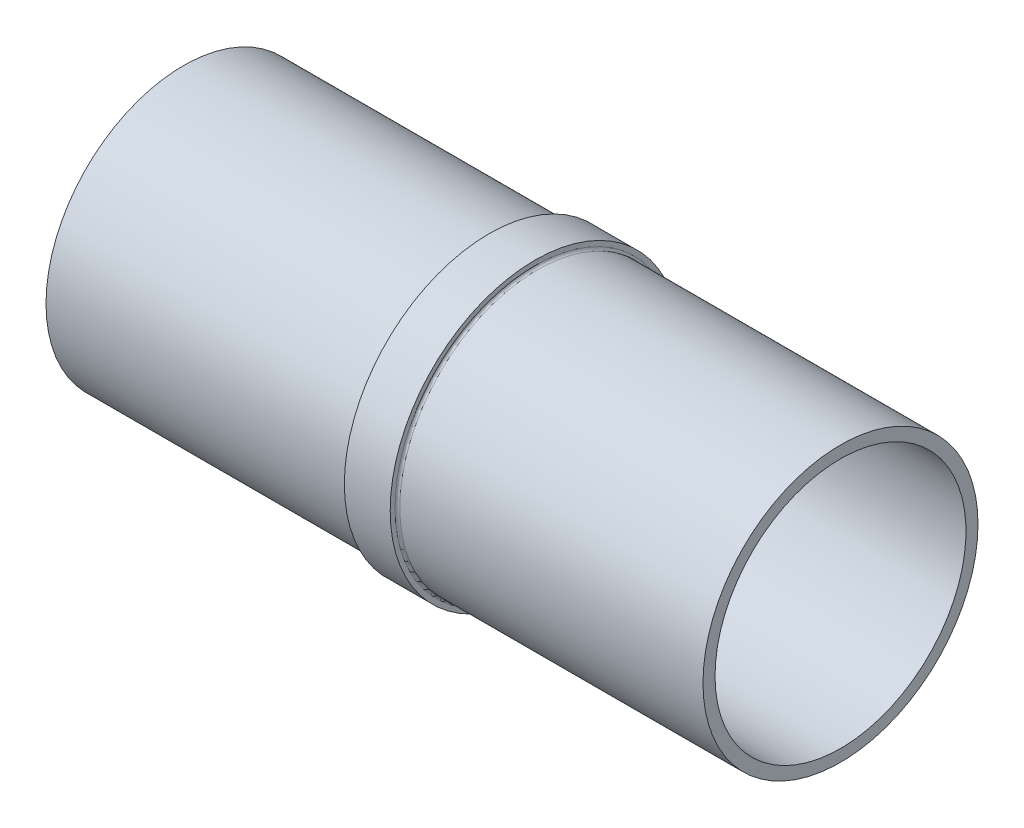
SolidWorks part; units mm, degrees
ref_plane "Front Plane" through (0, 0, 0) normal (0, 0, 1) x (1, 0, 0)
ref_plane "Top Plane" through (0, 0, 0) normal (0, 1, 0) x (1, 0, 0)
ref_plane "Right Plane" through (0, 0, 0) normal (1, 0, 0) x (0, 0, -1)
sketch "Sketch1" plane through (0, 0, 0) normal (0, 1, 0) x (1, 0, 0)
  line L1 (0, -34.1825) -> (0, 34.1825) construction
  line L2 (0, 52.15) -> (-74.2, 52.15)
  line L3 (-76.2, 50.15) -> (-76.2, 42.15)
  line L4 (-76.2, 42.15) -> (-95.7, 42.15)
  line L5 (-95.7, 42.15) -> (-95.7, 50.15)
  line L6 (-97.7, 52.15) -> (-273.05, 52.15)
  line L7 (-273.05, 52.15) -> (-273.05, 57.15)
  line L8 (-273.05, 57.15) -> (-147.05, 57.15)
  line L9 (-146.05, 58.15) -> (-146.05, 60.15)
  line L10 (-146.05, 60.15) -> (-127, 60.15)
  line L11 (-127, 60.15) -> (-127, 58.15)
  line L12 (-126, 57.15) -> (0, 57.15)
  line L13 (0, 57.15) -> (0, 52.15)
  arc A0 (-74.2, 52.15) -> (-76.2, 50.15) centre (-74.2, 50.15) ccw
  arc A1 (-95.7, 50.15) -> (-97.7, 52.15) centre (-97.7, 50.15) ccw
  arc A2 (-147.05, 57.15) -> (-146.05, 58.15) centre (-147.05, 58.15) ccw
  arc A3 (-127, 58.15) -> (-126, 57.15) centre (-126, 58.15) ccw
  point P18 (-76.2, 52.15)
  point P21 (-95.7, 52.15)
  point P24 (-146.05, 57.15)
  point P27 (-127, 57.15)
  dimension "D11" = 2
  dimension "D12" = 2
  dimension "D13" = 1
  dimension "D1" = 127
  dimension "D2" = 127
  dimension "D3" = 5
  dimension "D4" = 19.05
  dimension "D5" = 76.2
  dimension "D6" = 10
  dimension "D7" = 19.5
  dimension "D8" = 10
  dimension "D9" = 5
  dimension "D10" = 3
sketch "Sketch3" plane through (0, 0, 0) normal (0, 1, 0) x (1, 0, 0)
  line L0 (-185.7686, 0) -> (-52.5722, 0)
  line L1 (-150.1775, 0) -> (150.1775, 0) construction
revolve "Revolve1" add sketch "Sketch1" angle 360 about L0
